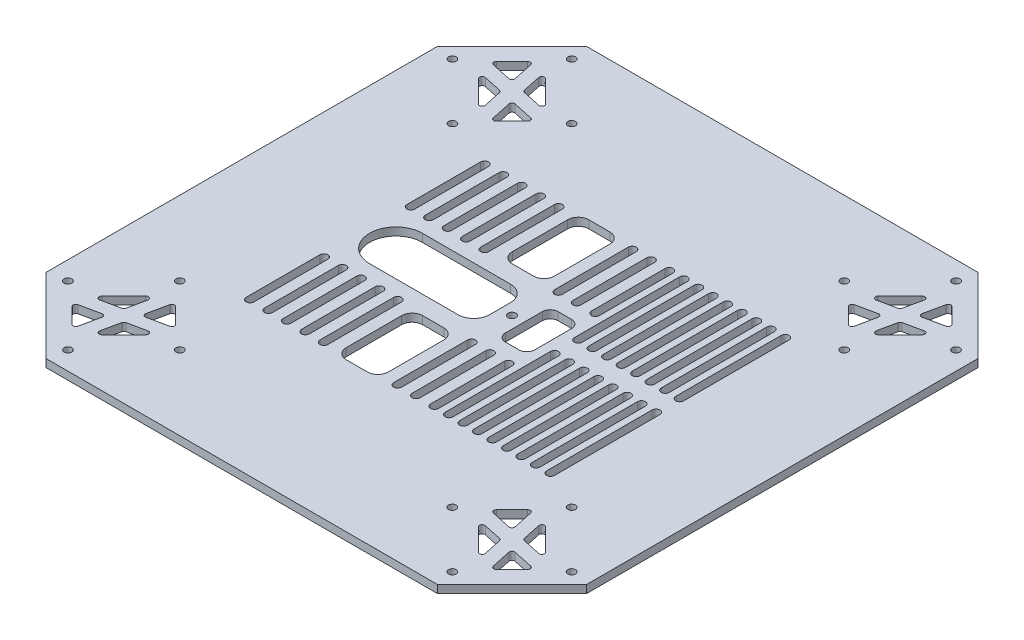
SolidWorks part; units mm, degrees
material "Thornel Mat VMA"
ref_plane "前视基准面" through (0, 0, 0) normal (0, 0, 1) x (1, 0, 0)
ref_plane "上视基准面" through (0, 0, 0) normal (0, 1, 0) x (1, 0, 0)
ref_plane "右视基准面" through (0, 0, 0) normal (1, 0, 0) x (0, 0, -1)
sketch "草图1" plane through (0, 0, 0) normal (0, 1, 0) x (1, 0, 0)
  line L0 (-74.2462, 102.5305) -> (-102.5305, 74.2462)
  line L1 (74.2462, 102.5305) -> (-74.2462, 102.5305)
  line L2 (102.5305, 74.2462) -> (102.5305, -74.2462)
  line L3 (74.2462, -102.5305) -> (-74.2462, -102.5305)
  line L4 (-102.5305, 74.2462) -> (-102.5305, -74.2462)
  line L5 (102.5305, 102.5305) -> (-102.5305, -102.5305) construction
  line L6 (102.5305, -102.5305) -> (-102.5305, 102.5305) construction
  line L7 (102.5305, -74.2462) -> (74.2462, -102.5305)
  line L8 (-102.5305, -74.2462) -> (-74.2462, -102.5305)
  line L9 (74.2462, 102.5305) -> (102.5305, 74.2462)
  line L10 (-102.5305, 102.5305) -> (-102.5305, -102.5305) construction
  line L11 (-102.5305, -102.5305) -> (102.5305, -102.5305) construction
  line L12 (102.5305, -102.5305) -> (102.5305, 102.5305) construction
  line L13 (102.5305, 102.5305) -> (-102.5305, 102.5305) construction
  point P0 (0, 0)
  dimension "D1" = 250
  dimension "D2" = 40
extrude "凸台-拉伸1" add sketch "草图1" along normal blind 3
hole_wizard "孔1" positions "草图4" profile "草图5" legacy
sketch "草图4" plane through (0, 3, 0) normal (0, 1, 0) x (1, 0, 0)
  point P0 (-95.5397, 72.9159)
  point P3 (-74.3265, 51.7027)
  point P6 (-51.6991, 74.3301)
  point P9 (-72.9123, 95.5433)
  point P16 (72.9159, 95.5397)
  point P17 (51.7027, 74.3265)
  point P18 (74.3301, 51.6991)
  point P19 (95.5433, 72.9123)
  point P20 (95.5397, -72.9159)
  point P21 (74.3265, -51.7027)
  point P22 (51.6991, -74.3301)
  point P23 (72.9123, -95.5433)
  point P24 (-72.9159, -95.5397)
  point P25 (-51.7027, -74.3265)
  point P26 (-74.3301, -51.6991)
  point P27 (-95.5433, -72.9123)
  dimension "D1" = 4
sketch "草图5" plane through (-95.5397, 3, -72.9159) normal (1, 0, 0) x (0, 0, 1)
  line L0 (0, 0) -> (0, 100)
  line L1 (0, 100) -> (1.45, 100)
  line L2 (1.45, 100) -> (1.45, 0)
  line L3 (1.45, 0) -> (0, 0)
  line L4 (0, 110) -> (0, -10) construction
  dimension "直径" = 2.9
  dimension "深度" = 100
sketch "草图7" plane through (0, 3, 0) normal (0, 1, 0) x (1, 0, 0)
  line L0 (-95.5397, 72.9159) -> (-51.6991, 74.3301) construction
  line L1 (-86.393, 80.4842) -> (-80.4806, 86.3966)
  line L2 (-84.1601, 71.4358) -> (-75.8066, 63.0823)
  line L3 (-71.4322, 84.1637) -> (-63.0787, 75.8102)
  line L4 (-66.7582, 60.8494) -> (-60.8458, 66.7618)
  line L5 (-89.8008, 77.0764) -> (-57.438, 70.1696) construction
  line L6 (-77.0728, 89.8044) -> (-70.166, 57.4416) construction
  line L7 (-49.2242, 67.6126) -> (-79.6109, 97.9993) construction
  line L8 (-74.2462, 102.5305) -> (-102.5305, 74.2462) construction
  line L9 (-85.8946, 78.7991) -> (-78.378, 77.1949)
  line L10 (-83.2443, 73.1208) -> (-76.36, 71.6516)
  line L11 (-87.6941, 79.1831) -> (-89.8008, 77.0764) construction
  line L12 (-89.8008, 77.0764) -> (-86.5509, 73.8265) construction
  line L13 (-60.6879, 73.4195) -> (-57.438, 70.1696) construction
  line L14 (-57.438, 70.1696) -> (-59.5447, 68.0629) construction
  line L15 (-67.4604, 74.8648) -> (-68.504, 69.975) construction
  line L16 (-73.6194, 73.623) -> (-67.2554, 79.987) construction
  line L17 (-74.1216, 63.9981) -> (-75.5908, 70.8824)
  line L18 (-68.4433, 61.3478) -> (-70.0475, 68.8644)
  line L19 (-70.8788, 75.5944) -> (-63.9945, 74.1252)
  line L20 (-77.1913, 78.3816) -> (-78.7955, 85.8982)
  line L21 (-68.8608, 70.0511) -> (-61.3442, 68.4469)
  line L22 (-71.648, 76.3636) -> (-73.1172, 83.2479)
  line L23 (80.4842, 86.393) -> (86.3966, 80.4806)
  line L24 (71.4358, 84.1601) -> (63.0823, 75.8066)
  line L25 (84.1637, 71.4322) -> (75.8102, 63.0787)
  line L26 (60.8494, 66.7582) -> (66.7618, 60.8458)
  line L27 (78.7991, 85.8946) -> (77.1949, 78.378)
  line L28 (73.1208, 83.2443) -> (71.6516, 76.36)
  line L29 (63.9981, 74.1216) -> (70.8824, 75.5908)
  line L30 (61.3478, 68.4433) -> (68.8644, 70.0475)
  line L31 (75.5944, 70.8788) -> (74.1252, 63.9945)
  line L32 (78.3816, 77.1913) -> (85.8982, 78.7955)
  line L33 (70.0511, 68.8608) -> (68.4469, 61.3442)
  line L34 (76.3636, 71.648) -> (83.2479, 73.1172)
  line L35 (72.9159, 95.5397) -> (74.3301, 51.6991) construction
  line L36 (77.0764, 89.8008) -> (70.1696, 57.438) construction
  line L37 (89.8044, 77.0728) -> (57.4416, 70.166) construction
  line L38 (79.1831, 87.6941) -> (77.0764, 89.8008) construction
  line L39 (77.0764, 89.8008) -> (73.8265, 86.5509) construction
  line L40 (73.4195, 60.6879) -> (70.1696, 57.438) construction
  line L41 (70.1696, 57.438) -> (68.0629, 59.5447) construction
  line L42 (74.8648, 67.4604) -> (69.975, 68.504) construction
  line L43 (73.623, 73.6194) -> (79.987, 67.2554) construction
  line L44 (86.393, -80.4842) -> (80.4806, -86.3966)
  line L45 (84.1601, -71.4358) -> (75.8066, -63.0823)
  line L46 (71.4322, -84.1637) -> (63.0787, -75.8102)
  line L47 (66.7582, -60.8494) -> (60.8458, -66.7618)
  line L48 (85.8946, -78.7991) -> (78.378, -77.1949)
  line L49 (83.2443, -73.1208) -> (76.36, -71.6516)
  line L50 (74.1216, -63.9981) -> (75.5908, -70.8824)
  line L51 (68.4433, -61.3478) -> (70.0475, -68.8644)
  line L52 (70.8788, -75.5944) -> (63.9945, -74.1252)
  line L53 (77.1913, -78.3816) -> (78.7955, -85.8982)
  line L54 (68.8608, -70.0511) -> (61.3442, -68.4469)
  line L55 (71.648, -76.3636) -> (73.1172, -83.2479)
  line L56 (95.5397, -72.9159) -> (51.6991, -74.3301) construction
  line L57 (89.8008, -77.0764) -> (57.438, -70.1696) construction
  line L58 (77.0728, -89.8044) -> (70.166, -57.4416) construction
  line L59 (87.6941, -79.1831) -> (89.8008, -77.0764) construction
  line L60 (89.8008, -77.0764) -> (86.5509, -73.8265) construction
  line L61 (60.6879, -73.4195) -> (57.438, -70.1696) construction
  line L62 (57.438, -70.1696) -> (59.5447, -68.0629) construction
  line L63 (67.4604, -74.8648) -> (68.504, -69.975) construction
  line L64 (73.6194, -73.623) -> (67.2554, -79.987) construction
  line L65 (-80.4842, -86.393) -> (-86.3966, -80.4806)
  line L66 (-71.4358, -84.1601) -> (-63.0823, -75.8066)
  line L67 (-84.1637, -71.4322) -> (-75.8102, -63.0787)
  line L68 (-60.8494, -66.7582) -> (-66.7618, -60.8458)
  line L69 (-78.7991, -85.8946) -> (-77.1949, -78.378)
  line L70 (-73.1208, -83.2443) -> (-71.6516, -76.36)
  line L71 (-63.9981, -74.1216) -> (-70.8824, -75.5908)
  line L72 (-61.3478, -68.4433) -> (-68.8644, -70.0475)
  line L73 (-75.5944, -70.8788) -> (-74.1252, -63.9945)
  line L74 (-78.3816, -77.1913) -> (-85.8982, -78.7955)
  line L75 (-70.0511, -68.8608) -> (-68.4469, -61.3442)
  line L76 (-76.3636, -71.648) -> (-83.2479, -73.1172)
  line L77 (-72.9159, -95.5397) -> (-74.3301, -51.6991) construction
  line L78 (-77.0764, -89.8008) -> (-70.1696, -57.438) construction
  line L79 (-89.8044, -77.0728) -> (-57.4416, -70.166) construction
  line L80 (-79.1831, -87.6941) -> (-77.0764, -89.8008) construction
  line L81 (-77.0764, -89.8008) -> (-73.8265, -86.5509) construction
  line L82 (-73.4195, -60.6879) -> (-70.1696, -57.438) construction
  line L83 (-70.1696, -57.438) -> (-68.0629, -59.5447) construction
  line L84 (-74.8648, -67.4604) -> (-69.975, -68.504) construction
  line L85 (-73.623, -73.6194) -> (-79.987, -67.2554) construction
  arc A0 (-63.0787, 75.8102) -> (-63.9945, 74.1252) centre (-63.7858, 75.1031) cw
  arc A1 (-70.8788, 75.5944) -> (-71.648, 76.3636) centre (-70.67, 76.5724) cw
  arc A2 (-71.4322, 84.1637) -> (-73.1172, 83.2479) centre (-72.1393, 83.4566) ccw
  arc A3 (-78.7955, 85.8982) -> (-80.4806, 86.3966) centre (-79.7735, 85.6895) ccw
  arc A4 (-85.8946, 78.7991) -> (-86.393, 80.4842) centre (-85.6859, 79.7771) cw
  arc A5 (-78.378, 77.1949) -> (-77.1913, 78.3816) centre (-78.1693, 78.1729) ccw
  arc A6 (-66.7582, 60.8494) -> (-68.4433, 61.3478) centre (-67.4653, 61.5565) cw
  arc A7 (-60.8458, 66.7618) -> (-61.3442, 68.4469) centre (-61.5529, 67.4689) ccw
  arc A8 (-68.8608, 70.0511) -> (-70.0475, 68.8644) centre (-69.0695, 69.0731) ccw
  arc A9 (-75.8066, 63.0823) -> (-74.1216, 63.9981) centre (-75.0995, 63.7894) ccw
  arc A10 (-75.5908, 70.8824) -> (-76.36, 71.6516) centre (-76.5688, 70.6736) ccw
  arc A11 (-83.2443, 73.1208) -> (-84.1601, 71.4358) centre (-83.453, 72.1429) ccw
  arc A12 (75.8102, 63.0787) -> (74.1252, 63.9945) centre (75.1031, 63.7858) cw
  arc A13 (75.5944, 70.8788) -> (76.3636, 71.648) centre (76.5724, 70.67) cw
  arc A14 (84.1637, 71.4322) -> (83.2479, 73.1172) centre (83.4566, 72.1393) ccw
  arc A15 (85.8982, 78.7955) -> (86.3966, 80.4806) centre (85.6895, 79.7735) ccw
  arc A16 (78.7991, 85.8946) -> (80.4842, 86.393) centre (79.7771, 85.6859) cw
  arc A17 (77.1949, 78.378) -> (78.3816, 77.1913) centre (78.1729, 78.1693) ccw
  arc A18 (60.8494, 66.7582) -> (61.3478, 68.4433) centre (61.5565, 67.4653) cw
  arc A19 (66.7618, 60.8458) -> (68.4469, 61.3442) centre (67.4689, 61.5529) ccw
  arc A20 (70.0511, 68.8608) -> (68.8644, 70.0475) centre (69.0731, 69.0695) ccw
  arc A21 (63.0823, 75.8066) -> (63.9981, 74.1216) centre (63.7894, 75.0995) ccw
  arc A22 (70.8824, 75.5908) -> (71.6516, 76.36) centre (70.6736, 76.5688) ccw
  arc A23 (73.1208, 83.2443) -> (71.4358, 84.1601) centre (72.1429, 83.453) ccw
  arc A24 (63.0787, -75.8102) -> (63.9945, -74.1252) centre (63.7858, -75.1031) cw
  arc A25 (70.8788, -75.5944) -> (71.648, -76.3636) centre (70.67, -76.5724) cw
  arc A26 (71.4322, -84.1637) -> (73.1172, -83.2479) centre (72.1393, -83.4566) ccw
  arc A27 (78.7955, -85.8982) -> (80.4806, -86.3966) centre (79.7735, -85.6895) ccw
  arc A28 (85.8946, -78.7991) -> (86.393, -80.4842) centre (85.6859, -79.7771) cw
  arc A29 (78.378, -77.1949) -> (77.1913, -78.3816) centre (78.1693, -78.1729) ccw
  arc A30 (66.7582, -60.8494) -> (68.4433, -61.3478) centre (67.4653, -61.5565) cw
  arc A31 (60.8458, -66.7618) -> (61.3442, -68.4469) centre (61.5529, -67.4689) ccw
  arc A32 (68.8608, -70.0511) -> (70.0475, -68.8644) centre (69.0695, -69.0731) ccw
  arc A33 (75.8066, -63.0823) -> (74.1216, -63.9981) centre (75.0995, -63.7894) ccw
  arc A34 (75.5908, -70.8824) -> (76.36, -71.6516) centre (76.5688, -70.6736) ccw
  arc A35 (83.2443, -73.1208) -> (84.1601, -71.4358) centre (83.453, -72.1429) ccw
  arc A36 (-75.8102, -63.0787) -> (-74.1252, -63.9945) centre (-75.1031, -63.7858) cw
  arc A37 (-75.5944, -70.8788) -> (-76.3636, -71.648) centre (-76.5724, -70.67) cw
  arc A38 (-84.1637, -71.4322) -> (-83.2479, -73.1172) centre (-83.4566, -72.1393) ccw
  arc A39 (-85.8982, -78.7955) -> (-86.3966, -80.4806) centre (-85.6895, -79.7735) ccw
  arc A40 (-78.7991, -85.8946) -> (-80.4842, -86.393) centre (-79.7771, -85.6859) cw
  arc A41 (-77.1949, -78.378) -> (-78.3816, -77.1913) centre (-78.1729, -78.1693) ccw
  arc A42 (-60.8494, -66.7582) -> (-61.3478, -68.4433) centre (-61.5565, -67.4653) cw
  arc A43 (-66.7618, -60.8458) -> (-68.4469, -61.3442) centre (-67.4689, -61.5529) ccw
  arc A44 (-70.0511, -68.8608) -> (-68.8644, -70.0475) centre (-69.0731, -69.0695) ccw
  arc A45 (-63.0823, -75.8066) -> (-63.9981, -74.1216) centre (-63.7894, -75.0995) ccw
  arc A46 (-70.8824, -75.5908) -> (-71.6516, -76.36) centre (-70.6736, -76.5688) ccw
  arc A47 (-73.1208, -83.2443) -> (-71.4358, -84.1601) centre (-72.1429, -83.453) ccw
  point P5 (-73.6194, 73.623)
  point P14 (-72.9123, 95.5433)
  point P21 (-67.9822, 72.4199)
  point P38 (-71.5127, 75.7297)
  point P41 (-73.8229, 86.5545)
  point P44 (-79.1795, 87.6977)
  point P50 (-76.8693, 76.8729)
  point P53 (-68.0593, 59.5483)
  point P59 (-70.3695, 70.3731)
  point P62 (-73.4159, 60.6915)
  point P73 (73.623, 73.6194)
  point P84 (72.4199, 67.9822)
  point P126 (73.6194, -73.623)
  point P137 (67.9822, -72.4199)
  point P179 (-73.623, -73.6194)
  point P190 (-72.4199, -67.9822)
  point P230 (0, 0)
  dimension "D4" = 1
  dimension "D1" = 7
  dimension "D2" = 7
  dimension "D3" = 5
  dimension "D5" = 4
extrude "切除-拉伸2" cut sketch "草图7" against normal through all both and the other way through all
sketch "草图8" plane through (0, 3, 0) normal (0, 1, 0) x (1, 0, 0)
  line L0 (-208.5651, 0) -> (0, 0) construction
  line L1 (-102.5305, -74.2462) -> (-50.5427, 0) construction
  line L3 (0, 0) -> (-88.3883, -88.3883) construction
  line L4 (-102.5305, -74.2462) -> (-74.2462, -102.5305) construction
  line L5 (0, 102.5305) -> (0, -102.5305) construction
  line L6 (74.2462, 102.5305) -> (-74.2462, 102.5305) construction
  line L7 (-74.2462, -102.5305) -> (74.2462, -102.5305) construction
  circle A0 centre (-208.5651, 0) radius 129.4443
  circle A2 centre (0, 208.5651) radius 129.4443
  circle A3 centre (208.5651, 0) radius 129.4443
  circle A4 centre (0, -208.5651) radius 129.4443
  point P28 (0, 0)
  dimension "D1" = 10
  dimension "D2" = 4
extrude "切除-拉伸3" cut sketch "草图8" against normal through all both and the other way through all
sketch "草图12" plane through (0, 3, 0) normal (0, 1, 0) x (1, 0, 0)
  line L0 (-74.2462, 102.5305) -> (-19.9669, 133.265)
  line L1 (-17.0105, 134.0438) -> (17.0105, 134.0438)
  line L2 (19.9669, 133.265) -> (74.2462, 102.5305)
  line L3 (0, 134.0438) -> (0, 0) construction
  line L4 (-74.2462, 102.5305) -> (-66.3304, 96.7253)
  line L5 (-62.6332, 98.7635) -> (-17.5957, 124.265)
  line L6 (-14.6394, 125.0438) -> (-10.5, 125.0438)
  line L7 (17.5957, 124.265) -> (62.6332, 98.7635)
  line L8 (66.1574, 95.9526) -> (74.2462, 102.5305)
  line L9 (-4.5, 119.0438) -> (-4.5, 81.2866)
  line L10 (-9.698, 64.0438) -> (9.698, 64.0438)
  line L11 (4.5, 81.2866) -> (4.5, 119.0438)
  line L12 (10.5, 125.0438) -> (14.6394, 125.0438)
  line L13 (-46.2735, 118.3694) -> (-41.839, 110.5377) construction
  line L14 (-4.5, 125.0438) -> (-4.5, 134.0438) construction
  line L15 (-66.3304, 96.7253) -> (-9.698, 64.0438)
  line L16 (9.698, 64.0438) -> (66.1574, 95.9526)
  line L17 (-4.5, 79.199) -> (4.5, 79.199) construction
  line L18 (-79.1207, 0) -> (79.1207, 0) construction
  line L19 (-4.5, -79.199) -> (4.5, -79.199) construction
  line L20 (-4.5, -125.0438) -> (-4.5, -134.0438) construction
  line L21 (-46.2735, -118.3694) -> (-41.839, -110.5377) construction
  line L22 (9.698, -64.0438) -> (66.1574, -95.9526)
  line L23 (-66.3304, -96.7253) -> (-9.698, -64.0438)
  line L24 (10.5, -125.0438) -> (14.6394, -125.0438)
  line L25 (4.5, -81.2866) -> (4.5, -119.0438)
  line L26 (-9.698, -64.0438) -> (9.698, -64.0438)
  line L27 (-4.5, -119.0438) -> (-4.5, -81.2866)
  line L28 (66.1574, -95.9526) -> (74.2462, -102.5305)
  line L29 (17.5957, -124.265) -> (62.6332, -98.7635)
  line L30 (-14.6394, -125.0438) -> (-10.5, -125.0438)
  line L31 (-62.6332, -98.7635) -> (-17.5957, -124.265)
  line L32 (-74.2462, -102.5305) -> (-66.3304, -96.7253)
  line L33 (19.9669, -133.265) -> (74.2462, -102.5305)
  line L34 (-17.0105, -134.0438) -> (17.0105, -134.0438)
  line L35 (-74.2462, -102.5305) -> (-19.9669, -133.265)
  arc A0 (-62.6152, 95.2727) -> (-6.602, 79.2892) centre (0, 208.5651) ccw
  arc A1 (-74.2462, 102.5305) -> (74.2462, 102.5305) centre (0, 208.5651) ccw construction
  arc A2 (6.602, 79.2892) -> (62.6152, 95.2727) centre (0, 208.5651) ccw
  arc A3 (-102.5305, -74.2462) -> (-102.5305, 74.2462) centre (-208.5651, 0) ccw construction
  arc A4 (102.5305, 74.2462) -> (102.5305, -74.2462) centre (208.5651, 0) ccw construction
  arc A5 (62.6152, 95.2727) -> (62.6332, 98.7635) centre (61.6478, 97.0231) ccw
  arc A6 (-62.6332, 98.7635) -> (-62.6152, 95.2727) centre (-61.6478, 97.0231) ccw
  arc A7 (6.602, 79.2892) -> (4.5, 81.2866) centre (6.5, 81.2866) cw
  arc A8 (-4.5, 81.2866) -> (-6.602, 79.2892) centre (-6.5, 81.2866) cw
  arc A9 (19.9669, 133.265) -> (17.0105, 134.0438) centre (17.0105, 128.0438) ccw
  arc A10 (-17.0105, 134.0438) -> (-19.9669, 133.265) centre (-17.0105, 128.0438) ccw
  arc A11 (-14.6394, 125.0438) -> (-17.5957, 124.265) centre (-14.6394, 119.0438) ccw
  arc A12 (17.5957, 124.265) -> (14.6394, 125.0438) centre (14.6394, 119.0438) ccw
  arc A13 (4.5, 119.0438) -> (10.5, 125.0438) centre (10.5, 119.0438) cw
  arc A14 (-4.5, 119.0438) -> (-10.5, 125.0438) centre (-10.5, 119.0438) ccw
  arc A15 (-4.5, -119.0438) -> (-10.5, -125.0438) centre (-10.5, -119.0438) cw
  arc A16 (4.5, -119.0438) -> (10.5, -125.0438) centre (10.5, -119.0438) ccw
  arc A17 (17.5957, -124.265) -> (14.6394, -125.0438) centre (14.6394, -119.0438) cw
  arc A18 (-14.6394, -125.0438) -> (-17.5957, -124.265) centre (-14.6394, -119.0438) cw
  arc A19 (-17.0105, -134.0438) -> (-19.9669, -133.265) centre (-17.0105, -128.0438) cw
  arc A20 (19.9669, -133.265) -> (17.0105, -134.0438) centre (17.0105, -128.0438) cw
  arc A21 (-4.5, -81.2866) -> (-6.602, -79.2892) centre (-6.5, -81.2866) ccw
  arc A22 (6.602, -79.2892) -> (4.5, -81.2866) centre (6.5, -81.2866) ccw
  arc A23 (-62.6332, -98.7635) -> (-62.6152, -95.2727) centre (-61.6478, -97.0231) cw
  arc A24 (62.6152, -95.2727) -> (62.6332, -98.7635) centre (61.6478, -97.0231) cw
  arc A25 (6.602, -79.2892) -> (62.6152, -95.2727) centre (0, -208.5651) cw
  arc A26 (-62.6152, -95.2727) -> (-6.602, -79.2892) centre (0, -208.5651) cw
  point P17 (0, 64.0438)
  point P24 (0, 79.199)
  point P40 (65.6946, 97.0301)
  point P43 (-65.6946, 97.0301)
  point P60 (4.5, 125.0438)
  point P107 (4.5, -125.0438)
  point P108 (-65.6946, -97.0301)
  point P109 (65.6946, -97.0301)
  point P110 (0, -79.199)
  point P111 (0, -64.0438)
  dimension "D4" = 2
  dimension "D5" = 2
  dimension "D6" = 6
  dimension "D1" = 70
  dimension "D2" = 9
  dimension "D3" = 9
sketch "草图15" plane through (0, 3, 0) normal (0, 1, 0) x (1, 0, 0)
  line L1 (-40.3412, 82.6837) -> (-31.9185, 62.6852)
  line L2 (44.6358, 80.4465) -> (36.2732, 60.2701)
  line L3 (-42.4295, -81.6317) -> (-34.5316, -61.2845)
  line L4 (41.391, -82.1632) -> (34.5498, -61.2743)
  arc A0 (-42.4295, -81.6317) -> (41.391, -82.1632) centre (0, 0) ccw
  arc A2 (-34.5316, -61.2845) -> (34.5498, -61.2743) centre (0, 0) ccw
  arc A3 (36.2732, 60.2701) -> (-31.9185, 62.6852) centre (0, 0) ccw
  arc A4 (44.6358, 80.4465) -> (-40.3412, 82.6837) centre (0, 0) ccw
  dimension "D1" = 92
extrude "凸台-拉伸3" add sketch "草图15" against normal up to surface (3 mm away) up to face at (-81.1939, 0, -81.1975)
sketch "草图18" plane through (0, 3, 0) normal (0, 1, 0) x (1, 0, 0)
  line L0 (-44.0207, 0) -> (12.6253, 0) construction
  line L1 (-44.0207, 10) -> (-10.5, 10)
  line L2 (-44.0207, -10) -> (-10.5, -10)
  line L3 (-54.0207, 0) -> (-79.1207, 0) construction
  line L5 (-4.5, -10) -> (4.5, -10) construction
  line L6 (-4.5, 4) -> (-4.5, -4)
  line L9 (-4.5, 10) -> (4.5, -10) construction
  line L10 (-4.5, -10) -> (4.5, 10) construction
  line L11 (-4.5, 10) -> (4.5, 10) construction
  arc A0 (-44.0207, 10) -> (-44.0207, -10) centre (-44.0207, 0) ccw
  arc A2 (102.5305, 74.2462) -> (102.5305, -74.2462) centre (208.5651, 0) ccw construction
  arc A3 (-10.5, 10) -> (-4.5, 4) centre (-10.5, 4) cw
  arc A4 (-102.5305, -74.2462) -> (-102.5305, 74.2462) centre (-208.5651, 0) ccw construction
  arc A8 (-4.5, -4) -> (-10.5, -10) centre (-10.5, -4) cw
  circle A9 centre (0, 0) radius 1.5
  point P3 (0, 0)
  point P5 (0, 0)
  point P9 (79.1207, 0)
  point P14 (-54.0207, 0)
  point P15 (0, 0)
  dimension "D5" = 6
extrude "切除-拉伸5" cut sketch "草图18" against normal through all both and the other way through all
sketch "草图20" plane through (0, 0, 0) normal (0, -1, 0) x (1, 0, 0)
  line L0 (-45.8783, 0) -> (59.1207, 0) construction
  line L1 (59.1207, 44.5) -> (59.1207, 4.5) construction
  line L2 (60.6207, 44.5) -> (60.6207, 4.5)
  line L3 (57.6207, 44.5) -> (57.6207, 4.5)
  line L4 (59.1207, -44.5) -> (59.1207, -4.5) construction
  line L5 (60.6207, -44.5) -> (60.6207, -4.5)
  line L6 (57.6207, -44.5) -> (57.6207, -4.5)
  line L7 (53.6207, 44.5) -> (53.6207, 4.5) construction
  line L8 (55.1207, 44.5) -> (55.1207, 4.5)
  line L9 (52.1207, 44.5) -> (52.1207, 4.5)
  line L10 (53.6207, -44.5) -> (53.6207, -4.5) construction
  line L11 (55.1207, -44.5) -> (55.1207, -4.5)
  line L12 (52.1207, -44.5) -> (52.1207, -4.5)
  line L13 (48.1207, 44.5) -> (48.1207, 4.5) construction
  line L14 (49.6207, 44.5) -> (49.6207, 4.5)
  line L15 (46.6207, 44.5) -> (46.6207, 4.5)
  line L16 (48.1207, -44.5) -> (48.1207, -4.5) construction
  line L17 (49.6207, -44.5) -> (49.6207, -4.5)
  line L18 (46.6207, -44.5) -> (46.6207, -4.5)
  line L19 (42.6207, 44.5) -> (42.6207, 4.5) construction
  line L20 (44.1207, 44.5) -> (44.1207, 4.5)
  line L21 (41.1207, 44.5) -> (41.1207, 4.5)
  line L22 (42.6207, -44.5) -> (42.6207, -4.5) construction
  line L23 (44.1207, -44.5) -> (44.1207, -4.5)
  line L24 (41.1207, -44.5) -> (41.1207, -4.5)
  line L25 (37.1207, 44.5) -> (37.1207, 4.5) construction
  line L26 (38.6207, 44.5) -> (38.6207, 4.5)
  line L27 (35.6207, 44.5) -> (35.6207, 4.5)
  line L28 (37.1207, -44.5) -> (37.1207, -4.5) construction
  line L29 (38.6207, -44.5) -> (38.6207, -4.5)
  line L30 (35.6207, -44.5) -> (35.6207, -4.5)
  line L31 (31.6207, 44.5) -> (31.6207, 4.5) construction
  line L32 (33.1207, 44.5) -> (33.1207, 4.5)
  line L33 (30.1207, 44.5) -> (30.1207, 4.5)
  line L34 (31.6207, -44.5) -> (31.6207, -4.5) construction
  line L35 (33.1207, -44.5) -> (33.1207, -4.5)
  line L36 (30.1207, -44.5) -> (30.1207, -4.5)
  line L37 (26.1207, 44.5) -> (26.1207, 4.5) construction
  line L38 (27.6207, 44.5) -> (27.6207, 4.5)
  line L39 (24.6207, 44.5) -> (24.6207, 4.5)
  line L40 (26.1207, -44.5) -> (26.1207, -4.5) construction
  line L41 (27.6207, -44.5) -> (27.6207, -4.5)
  line L42 (24.6207, -44.5) -> (24.6207, -4.5)
  line L43 (20.6207, 44.5) -> (20.6207, 4.5) construction
  line L44 (22.1207, 44.5) -> (22.1207, 4.5)
  line L45 (19.1207, 44.5) -> (19.1207, 4.5)
  line L46 (20.6207, -44.5) -> (20.6207, -4.5) construction
  line L47 (22.1207, -44.5) -> (22.1207, -4.5)
  line L48 (19.1207, -44.5) -> (19.1207, -4.5)
  line L238 (15.1207, -44.5) -> (15.1207, -4.5) construction
  line L239 (13.6207, -44.5) -> (13.6207, -4.5) [skipped]
  line L240 (16.6207, -44.5) -> (16.6207, -4.5) [skipped]
  line L241 (15.1207, 44.5) -> (15.1207, 4.5) construction
  line L242 (16.6207, 44.5) -> (16.6207, 4.5) [skipped]
  line L243 (13.6207, 44.5) -> (13.6207, 4.5) [skipped]
  line L244 (15.1207, -44.5) -> (15.1207, -4.5) construction
  line L245 (13.6207, -44.5) -> (13.6207, -4.5) [skipped]
  line L246 (16.6207, -44.5) -> (16.6207, -4.5) [skipped]
  line L247 (15.1207, 44.5) -> (15.1207, 4.5) construction
  line L248 (16.6207, 44.5) -> (16.6207, 4.5) [skipped]
  line L249 (13.6207, 44.5) -> (13.6207, 4.5) [skipped]
  arc A0 (60.6207, 44.5) -> (57.6207, 44.5) centre (59.1207, 44.5) ccw
  arc A1 (57.6207, 4.5) -> (60.6207, 4.5) centre (59.1207, 4.5) ccw
  arc A2 (60.6207, -44.5) -> (57.6207, -44.5) centre (59.1207, -44.5) cw
  arc A3 (57.6207, -4.5) -> (60.6207, -4.5) centre (59.1207, -4.5) cw
  arc A4 (55.1207, 44.5) -> (52.1207, 44.5) centre (53.6207, 44.5) ccw
  arc A5 (52.1207, 4.5) -> (55.1207, 4.5) centre (53.6207, 4.5) ccw
  arc A6 (55.1207, -44.5) -> (52.1207, -44.5) centre (53.6207, -44.5) cw
  arc A7 (52.1207, -4.5) -> (55.1207, -4.5) centre (53.6207, -4.5) cw
  arc A8 (49.6207, 44.5) -> (46.6207, 44.5) centre (48.1207, 44.5) ccw
  arc A9 (46.6207, 4.5) -> (49.6207, 4.5) centre (48.1207, 4.5) ccw
  arc A10 (49.6207, -44.5) -> (46.6207, -44.5) centre (48.1207, -44.5) cw
  arc A11 (46.6207, -4.5) -> (49.6207, -4.5) centre (48.1207, -4.5) cw
  arc A12 (44.1207, 44.5) -> (41.1207, 44.5) centre (42.6207, 44.5) ccw
  arc A13 (41.1207, 4.5) -> (44.1207, 4.5) centre (42.6207, 4.5) ccw
  arc A14 (44.1207, -44.5) -> (41.1207, -44.5) centre (42.6207, -44.5) cw
  arc A15 (41.1207, -4.5) -> (44.1207, -4.5) centre (42.6207, -4.5) cw
  arc A16 (38.6207, 44.5) -> (35.6207, 44.5) centre (37.1207, 44.5) ccw
  arc A17 (35.6207, 4.5) -> (38.6207, 4.5) centre (37.1207, 4.5) ccw
  arc A18 (38.6207, -44.5) -> (35.6207, -44.5) centre (37.1207, -44.5) cw
  arc A19 (35.6207, -4.5) -> (38.6207, -4.5) centre (37.1207, -4.5) cw
  arc A20 (33.1207, 44.5) -> (30.1207, 44.5) centre (31.6207, 44.5) ccw
  arc A21 (30.1207, 4.5) -> (33.1207, 4.5) centre (31.6207, 4.5) ccw
  arc A22 (33.1207, -44.5) -> (30.1207, -44.5) centre (31.6207, -44.5) cw
  arc A23 (30.1207, -4.5) -> (33.1207, -4.5) centre (31.6207, -4.5) cw
  arc A24 (27.6207, 44.5) -> (24.6207, 44.5) centre (26.1207, 44.5) ccw
  arc A25 (24.6207, 4.5) -> (27.6207, 4.5) centre (26.1207, 4.5) ccw
  arc A26 (27.6207, -44.5) -> (24.6207, -44.5) centre (26.1207, -44.5) cw
  arc A27 (24.6207, -4.5) -> (27.6207, -4.5) centre (26.1207, -4.5) cw
  arc A28 (22.1207, 44.5) -> (19.1207, 44.5) centre (20.6207, 44.5) ccw
  arc A29 (19.1207, 4.5) -> (22.1207, 4.5) centre (20.6207, 4.5) ccw
  arc A30 (22.1207, -44.5) -> (19.1207, -44.5) centre (20.6207, -44.5) cw
  arc A31 (19.1207, -4.5) -> (22.1207, -4.5) centre (20.6207, -4.5) cw
  arc A32 (102.5305, 74.2462) -> (102.5305, -74.2462) centre (208.5651, 0) ccw construction
  arc A162 (13.6207, -44.5) -> (16.6207, -44.5) centre (15.1207, -44.5) ccw [skipped]
  arc A163 (16.6207, -4.5) -> (13.6207, -4.5) centre (15.1207, -4.5) ccw [skipped]
  arc A164 (16.6207, 44.5) -> (13.6207, 44.5) centre (15.1207, 44.5) ccw [skipped]
  arc A165 (13.6207, 4.5) -> (16.6207, 4.5) centre (15.1207, 4.5) ccw [skipped]
  point P5 (59.1207, 24.5)
  point P11 (59.1207, 3)
  point P13 (59.1207, -24.5)
  point P18 (59.1207, -3)
  point P19 (79.1207, 0)
  point P20 (16.0965, -28.5688)
  point P23 (53.6207, 24.5)
  point P29 (53.6207, 3)
  point P31 (53.6207, -24.5)
  point P36 (53.6207, -3)
  point P39 (48.1207, 24.5)
  point P45 (48.1207, 3)
  point P47 (48.1207, -24.5)
  point P52 (48.1207, -3)
  point P55 (42.6207, 24.5)
  point P61 (42.6207, 3)
  point P63 (42.6207, -24.5)
  point P68 (42.6207, -3)
  point P71 (37.1207, 24.5)
  point P77 (37.1207, 3)
  point P79 (37.1207, -24.5)
  point P84 (37.1207, -3)
  point P87 (31.6207, 24.5)
  point P93 (31.6207, 3)
  point P95 (31.6207, -24.5)
  point P100 (31.6207, -3)
  point P103 (26.1207, 24.5)
  point P109 (26.1207, 3)
  point P111 (26.1207, -24.5)
  point P116 (26.1207, -3)
  point P119 (20.6207, 24.5)
  point P125 (20.6207, 3)
  point P127 (20.6207, -24.5)
  point P132 (20.6207, -3)
  point P135 (21.0655, -24.0622)
  point P140 (15.1207, -3)
  point P142 (15.1207, 3)
  point P149 (21.0655, 24.0622)
  point P157 (21.0655, -24.0622)
  point P164 (21.0655, 24.0622)
  point P171 (21.0655, -24.0622)
  point P178 (21.0655, 24.0622)
  point P185 (21.0655, -24.0622)
  point P192 (21.0655, 24.0622)
  point P199 (21.0655, -24.0622)
  point P206 (21.0655, 24.0622)
  point P213 (21.0655, -24.0622)
  point P220 (21.0655, 24.0622)
  point P227 (16.1207, -24.0622)
  point P234 (16.1207, 24.0622)
  point P241 (16.1207, -24.0622)
  point P248 (16.1207, 24.0622)
  point P255 (11.1207, -24.0622)
  point P262 (11.1207, 24.0622)
  point P269 (11.1207, -24.0622)
  point P276 (11.1207, 24.0622)
  point P283 (11.1207, -29.0622)
  point P290 (11.1207, 29.0622)
  point P297 (11.1207, -29.0622)
  point P304 (11.1207, 29.0622)
  point P311 (15.1207, -29)
  point P318 (15.1207, 29)
  point P325 (15.1207, -29)
  point P332 (15.1207, 29)
  point P339 (15.1207, -24)
  point P346 (15.1207, 24)
  point P353 (15.1207, -24)
  point P360 (15.1207, 24)
  point P367 (15.1207, -24.5)
  point P374 (15.1207, 24.5)
  point P381 (15.1207, -24.5)
  point P388 (15.1207, 24.5)
  point P395 (15.1207, -24.5)
  point P402 (15.1207, 24.5)
  point P409 (15.1207, -24.5)
  point P416 (15.1207, 24.5)
  point P423 (15.1207, -24.5)
  point P430 (15.1207, 24.5)
  point P437 (15.1207, -24.5)
  point P444 (15.1207, 24.5)
  point P451 (15.1207, -24.5)
  point P458 (15.1207, 24.5)
  point P465 (15.1207, -24.5)
  point P472 (15.1207, 24.5)
  point P479 (15.1207, -24.5)
  point P486 (15.1207, 24.5)
  point P493 (15.1207, -24.5)
  point P500 (15.1207, 24.5)
  point P507 (15.1207, -24.5)
  point P514 (15.1207, 24.5)
  point P521 (15.1207, -24.5)
  point P528 (15.1207, 24.5)
  point P535 (15.1207, -24.5)
  point P542 (15.1207, 24.5)
  point P549 (15.1207, -24.5)
  point P556 (15.1207, 24.5)
  point P563 (15.1207, -24.5)
  point P570 (15.1207, 24.5)
  point P577 (15.1207, -24.5)
  point P584 (15.1207, 24.5)
  point P591 (15.1207, -24.5)
  point P598 (15.1207, 24.5)
  dimension "D2" = 9
  dimension "D5" = 1.5
  dimension "D1" = 3
  dimension "D3" = 40
  dimension "D4" = 20
  dimension "D6" = 5.5
extrude "切除-拉伸7" cut sketch "草图20" against normal through all both and the other way through all
sketch "草图21" plane through (0, 3, 0) normal (0, 1, 0) x (1, 0, 0)
  line L0 (15.1207, 16.5) -> (15.1207, 44.5) construction
  line L1 (13.6207, 16.5) -> (13.6207, 44.5)
  line L2 (16.6207, 16.5) -> (16.6207, 44.5)
  line L3 (15.1207, 44.5) -> (20.6207, 44.5) construction
  line L4 (19.1207, 4.5) -> (19.1207, 44.5) construction
  line L5 (-13.3448, 10) -> (19.1207, 10) construction
  line L6 (-10.5, 10) -> (-44.0207, 10) construction
  line L7 (0, 0) -> (29.0659, 0) construction
  line L8 (15.1207, -16.5) -> (15.1207, -44.5) construction
  line L9 (16.6207, -16.5) -> (16.6207, -44.5)
  line L10 (13.6207, -16.5) -> (13.6207, -44.5)
  line L12 (8.1207, 44.5) -> (13.6207, 44.5) construction
  line L14 (8.1207, 16.5) -> (8.1207, 44.5) construction
  line L15 (6.6207, 16.5) -> (6.6207, 44.5)
  line L16 (9.6207, 16.5) -> (9.6207, 44.5)
  line L17 (8.1207, -16.5) -> (8.1207, -44.5) construction
  line L18 (9.6207, -16.5) -> (9.6207, -44.5)
  line L19 (6.6207, -16.5) -> (6.6207, -44.5)
  line L20 (1.1207, 44.5) -> (6.6207, 44.5) construction
  line L21 (6.6207, -44.5) -> (1.1207, -44.5) construction
  line L22 (1.1207, 16.5) -> (1.1207, 44.5) construction
  line L23 (-0.3793, 16.5) -> (-0.3793, 44.5)
  line L24 (2.6207, 16.5) -> (2.6207, 44.5)
  line L25 (1.1207, -16.5) -> (1.1207, -44.5) construction
  line L26 (2.6207, -16.5) -> (2.6207, -44.5)
  line L27 (-0.3793, -16.5) -> (-0.3793, -44.5)
  line L28 (-5.8793, 44.5) -> (-0.3793, 44.5) construction
  line L29 (-0.3793, -44.5) -> (-5.8793, -44.5) construction
  line L52 (-26.8793, 44.5) -> (-21.3793, 44.5) construction
  line L53 (-21.3793, -44.5) -> (-26.8793, -44.5) construction
  line L54 (-33.8793, 44.5) -> (-28.3793, 44.5) construction
  line L55 (-28.3793, -44.5) -> (-33.8793, -44.5) construction
  line L56 (-7, 0) -> (22.0659, 0) construction
  line L57 (-26.8793, 16.5) -> (-26.8793, 44.5) construction
  line L58 (-28.3793, 16.5) -> (-28.3793, 44.5)
  line L59 (-25.3793, 16.5) -> (-25.3793, 44.5)
  line L60 (-26.8793, -16.5) -> (-26.8793, -44.5) construction
  line L61 (-25.3793, -16.5) -> (-25.3793, -44.5)
  line L62 (-28.3793, -16.5) -> (-28.3793, -44.5)
  line L63 (-40.8793, 44.5) -> (-35.3793, 44.5) construction
  line L64 (-35.3793, -44.5) -> (-40.8793, -44.5) construction
  line L65 (-14, 0) -> (15.0659, 0) construction
  line L66 (-33.8793, 16.5) -> (-33.8793, 44.5) construction
  line L67 (-35.3793, 16.5) -> (-35.3793, 44.5)
  line L68 (-32.3793, 16.5) -> (-32.3793, 44.5)
  line L69 (-33.8793, -16.5) -> (-33.8793, -44.5) construction
  line L70 (-32.3793, -16.5) -> (-32.3793, -44.5)
  line L71 (-35.3793, -16.5) -> (-35.3793, -44.5)
  line L72 (-47.8793, 44.5) -> (-42.3793, 44.5) construction
  line L73 (-42.3793, -44.5) -> (-47.8793, -44.5) construction
  line L74 (-21, 0) -> (8.0659, 0) construction
  line L75 (-40.8793, 16.5) -> (-40.8793, 44.5) construction
  line L76 (-42.3793, 16.5) -> (-42.3793, 44.5)
  line L77 (-39.3793, 16.5) -> (-39.3793, 44.5)
  line L78 (-40.8793, -16.5) -> (-40.8793, -44.5) construction
  line L79 (-39.3793, -16.5) -> (-39.3793, -44.5)
  line L80 (-42.3793, -16.5) -> (-42.3793, -44.5)
  line L81 (-54.8793, 44.5) -> (-49.3793, 44.5) construction
  line L82 (-49.3793, -44.5) -> (-54.8793, -44.5) construction
  line L83 (-28, 0) -> (1.0659, 0) construction
  line L84 (-47.8793, 16.5) -> (-47.8793, 44.5) construction
  line L85 (-49.3793, 16.5) -> (-49.3793, 44.5)
  line L86 (-46.3793, 16.5) -> (-46.3793, 44.5)
  line L87 (-47.8793, -16.5) -> (-47.8793, -44.5) construction
  line L88 (-46.3793, -16.5) -> (-46.3793, -44.5)
  line L89 (-49.3793, -16.5) -> (-49.3793, -44.5)
  line L90 (-61.8793, 44.5) -> (-56.3793, 44.5) construction
  line L91 (-56.3793, -44.5) -> (-61.8793, -44.5) construction
  line L92 (-35, 0) -> (-5.9341, 0) construction
  line L93 (-54.8793, 16.5) -> (-54.8793, 44.5) construction
  line L94 (-56.3793, 16.5) -> (-56.3793, 44.5)
  line L95 (-33.8793, 44.5) -> (-28.3793, 44.5) construction
  line L97 (-40.8793, 44.5) -> (-35.3793, 44.5) construction
  line L99 (-47.8793, 44.5) -> (-42.3793, 44.5) construction
  line L101 (-54.8793, 44.5) -> (-49.3793, 44.5) construction
  line L163 (-53.3793, 16.5) -> (-53.3793, 44.5)
  line L164 (-54.8793, -16.5) -> (-54.8793, -44.5) construction
  line L165 (-53.3793, -16.5) -> (-53.3793, -44.5)
  line L166 (-56.3793, -16.5) -> (-56.3793, -44.5)
  line L227 (-12.8793, 44.5) -> (-7.3793, 44.5) construction
  line L229 (-19.8793, 44.5) -> (-14.3793, 44.5) construction
  line L1000 (-5.8793, -16.5) -> (-5.8793, -44.5) construction
  line L1001 (-4.3793, -16.5) -> (-4.3793, -44.5) [skipped]
  line L1002 (-7.3793, -16.5) -> (-7.3793, -44.5) [skipped]
  line L1003 (-12.8793, 16.5) -> (-12.8793, 44.5) construction
  line L1004 (-14.3793, 16.5) -> (-14.3793, 44.5) [skipped]
  line L1005 (-11.3793, 16.5) -> (-11.3793, 44.5) [skipped]
  line L1006 (-12.8793, -16.5) -> (-12.8793, -44.5) construction
  line L1007 (-11.3793, -16.5) -> (-11.3793, -44.5) [skipped]
  line L1008 (-14.3793, -16.5) -> (-14.3793, -44.5) [skipped]
  line L1009 (-19.8793, 16.5) -> (-19.8793, 44.5) construction
  line L1010 (-21.3793, 16.5) -> (-21.3793, 44.5) [skipped]
  line L1011 (-18.3793, 16.5) -> (-18.3793, 44.5) [skipped]
  line L1012 (-19.8793, -16.5) -> (-19.8793, -44.5) construction
  line L1013 (-18.3793, -16.5) -> (-18.3793, -44.5) [skipped]
  line L1014 (-21.3793, -16.5) -> (-21.3793, -44.5) [skipped]
  line L1015 (-5.8793, 16.5) -> (-5.8793, 44.5) construction
  line L1016 (-7.3793, 16.5) -> (-7.3793, 44.5) [skipped]
  line L1017 (-4.3793, 16.5) -> (-4.3793, 44.5) [skipped]
  line L1018 (-26.8793, -16.5) -> (-26.8793, -44.5) construction
  line L1019 (-25.3793, -16.5) -> (-25.3793, -44.5) [skipped]
  line L1020 (-28.3793, -16.5) -> (-28.3793, -44.5) [skipped]
  line L1021 (-33.8793, 16.5) -> (-33.8793, 44.5) construction
  line L1022 (-35.3793, 16.5) -> (-35.3793, 44.5) [skipped]
  line L1023 (-32.3793, 16.5) -> (-32.3793, 44.5) [skipped]
  line L1024 (-33.8793, -16.5) -> (-33.8793, -44.5) construction
  line L1025 (-32.3793, -16.5) -> (-32.3793, -44.5) [skipped]
  line L1026 (-35.3793, -16.5) -> (-35.3793, -44.5) [skipped]
  line L1027 (-40.8793, 16.5) -> (-40.8793, 44.5) construction
  line L1028 (-42.3793, 16.5) -> (-42.3793, 44.5) [skipped]
  line L1029 (-39.3793, 16.5) -> (-39.3793, 44.5) [skipped]
  line L1030 (-40.8793, -16.5) -> (-40.8793, -44.5) construction
  line L1031 (-39.3793, -16.5) -> (-39.3793, -44.5) [skipped]
  line L1032 (-42.3793, -16.5) -> (-42.3793, -44.5) [skipped]
  line L1033 (-47.8793, 16.5) -> (-47.8793, 44.5) construction
  line L1034 (-49.3793, 16.5) -> (-49.3793, 44.5) [skipped]
  line L1035 (-46.3793, 16.5) -> (-46.3793, 44.5) [skipped]
  line L1036 (-47.8793, -16.5) -> (-47.8793, -44.5) construction
  line L1037 (-46.3793, -16.5) -> (-46.3793, -44.5) [skipped]
  line L1038 (-49.3793, -16.5) -> (-49.3793, -44.5) [skipped]
  line L1039 (-54.8793, 16.5) -> (-54.8793, 44.5) construction
  line L1040 (-56.3793, 16.5) -> (-56.3793, 44.5) [skipped]
  line L1041 (-53.3793, 16.5) -> (-53.3793, 44.5) [skipped]
  line L1042 (-54.8793, -16.5) -> (-54.8793, -44.5) construction
  line L1043 (-53.3793, -16.5) -> (-53.3793, -44.5) [skipped]
  line L1044 (-56.3793, -16.5) -> (-56.3793, -44.5) [skipped]
  line L1045 (-26.8793, 16.5) -> (-26.8793, 44.5) construction
  line L1046 (-28.3793, 16.5) -> (-28.3793, 44.5) [skipped]
  line L1047 (-25.3793, 16.5) -> (-25.3793, 44.5) [skipped]
  line L1048 (-5.8793, -16.5) -> (-5.8793, -44.5) construction
  line L1049 (-4.3793, -16.5) -> (-4.3793, -44.5) [skipped]
  line L1050 (-7.3793, -16.5) -> (-7.3793, -44.5) [skipped]
  line L1051 (-12.8793, 16.5) -> (-12.8793, 44.5) construction
  line L1052 (-14.3793, 16.5) -> (-14.3793, 44.5) [skipped]
  line L1053 (-11.3793, 16.5) -> (-11.3793, 44.5) [skipped]
  line L1054 (-12.8793, -16.5) -> (-12.8793, -44.5) construction
  line L1055 (-11.3793, -16.5) -> (-11.3793, -44.5) [skipped]
  line L1056 (-14.3793, -16.5) -> (-14.3793, -44.5) [skipped]
  line L1057 (-19.8793, 16.5) -> (-19.8793, 44.5) construction
  line L1058 (-21.3793, 16.5) -> (-21.3793, 44.5) [skipped]
  line L1059 (-18.3793, 16.5) -> (-18.3793, 44.5) [skipped]
  line L1060 (-19.8793, -16.5) -> (-19.8793, -44.5) construction
  line L1061 (-18.3793, -16.5) -> (-18.3793, -44.5) [skipped]
  line L1062 (-21.3793, -16.5) -> (-21.3793, -44.5) [skipped]
  line L1063 (-5.8793, 16.5) -> (-5.8793, 44.5) construction
  line L1064 (-7.3793, 16.5) -> (-7.3793, 44.5) [skipped]
  line L1065 (-4.3793, 16.5) -> (-4.3793, 44.5) [skipped]
  line L1066 (-26.8793, -16.5) -> (-26.8793, -44.5) construction
  line L1067 (-25.3793, -16.5) -> (-25.3793, -44.5) [skipped]
  line L1068 (-28.3793, -16.5) -> (-28.3793, -44.5) [skipped]
  line L1069 (-33.8793, 16.5) -> (-33.8793, 44.5) construction
  line L1070 (-35.3793, 16.5) -> (-35.3793, 44.5) [skipped]
  line L1071 (-32.3793, 16.5) -> (-32.3793, 44.5) [skipped]
  line L1072 (-33.8793, -16.5) -> (-33.8793, -44.5) construction
  line L1073 (-32.3793, -16.5) -> (-32.3793, -44.5) [skipped]
  line L1074 (-35.3793, -16.5) -> (-35.3793, -44.5) [skipped]
  line L1075 (-40.8793, 16.5) -> (-40.8793, 44.5) construction
  line L1076 (-42.3793, 16.5) -> (-42.3793, 44.5) [skipped]
  line L1077 (-39.3793, 16.5) -> (-39.3793, 44.5) [skipped]
  line L1078 (-40.8793, -16.5) -> (-40.8793, -44.5) construction
  line L1079 (-39.3793, -16.5) -> (-39.3793, -44.5) [skipped]
  line L1080 (-42.3793, -16.5) -> (-42.3793, -44.5) [skipped]
  line L1081 (-47.8793, 16.5) -> (-47.8793, 44.5) construction
  line L1082 (-49.3793, 16.5) -> (-49.3793, 44.5) [skipped]
  line L1083 (-46.3793, 16.5) -> (-46.3793, 44.5) [skipped]
  line L1084 (-47.8793, -16.5) -> (-47.8793, -44.5) construction
  line L1085 (-46.3793, -16.5) -> (-46.3793, -44.5) [skipped]
  line L1086 (-49.3793, -16.5) -> (-49.3793, -44.5) [skipped]
  line L1087 (-54.8793, 16.5) -> (-54.8793, 44.5) construction
  line L1088 (-56.3793, 16.5) -> (-56.3793, 44.5) [skipped]
  line L1089 (-53.3793, 16.5) -> (-53.3793, 44.5) [skipped]
  line L1090 (-54.8793, -16.5) -> (-54.8793, -44.5) construction
  line L1091 (-53.3793, -16.5) -> (-53.3793, -44.5) [skipped]
  line L1092 (-56.3793, -16.5) -> (-56.3793, -44.5) [skipped]
  line L1093 (-26.8793, 16.5) -> (-26.8793, 44.5) construction
  line L1094 (-28.3793, 16.5) -> (-28.3793, 44.5) [skipped]
  line L1095 (-25.3793, 16.5) -> (-25.3793, 44.5) [skipped]
  arc A0 (13.6207, 16.5) -> (16.6207, 16.5) centre (15.1207, 16.5) ccw
  arc A1 (16.6207, 44.5) -> (13.6207, 44.5) centre (15.1207, 44.5) ccw
  arc A2 (16.6207, -16.5) -> (13.6207, -16.5) centre (15.1207, -16.5) ccw
  arc A3 (13.6207, -44.5) -> (16.6207, -44.5) centre (15.1207, -44.5) ccw
  arc A5 (19.1207, -44.5) -> (22.1207, -44.5) centre (20.6207, -44.5) ccw construction
  arc A6 (6.6207, 16.5) -> (9.6207, 16.5) centre (8.1207, 16.5) ccw
  arc A7 (9.6207, 44.5) -> (6.6207, 44.5) centre (8.1207, 44.5) ccw
  arc A8 (9.6207, -16.5) -> (6.6207, -16.5) centre (8.1207, -16.5) ccw
  arc A9 (6.6207, -44.5) -> (9.6207, -44.5) centre (8.1207, -44.5) ccw
  arc A10 (-0.3793, 16.5) -> (2.6207, 16.5) centre (1.1207, 16.5) ccw
  arc A11 (2.6207, 44.5) -> (-0.3793, 44.5) centre (1.1207, 44.5) ccw
  arc A12 (2.6207, -16.5) -> (-0.3793, -16.5) centre (1.1207, -16.5) ccw
  arc A13 (-0.3793, -44.5) -> (2.6207, -44.5) centre (1.1207, -44.5) ccw
  arc A26 (-28.3793, 16.5) -> (-25.3793, 16.5) centre (-26.8793, 16.5) ccw
  arc A27 (-25.3793, 44.5) -> (-28.3793, 44.5) centre (-26.8793, 44.5) ccw
  arc A28 (-25.3793, -16.5) -> (-28.3793, -16.5) centre (-26.8793, -16.5) ccw
  arc A29 (-28.3793, -44.5) -> (-25.3793, -44.5) centre (-26.8793, -44.5) ccw
  arc A30 (-35.3793, 16.5) -> (-32.3793, 16.5) centre (-33.8793, 16.5) ccw
  arc A31 (-32.3793, 44.5) -> (-35.3793, 44.5) centre (-33.8793, 44.5) ccw
  arc A32 (-32.3793, -16.5) -> (-35.3793, -16.5) centre (-33.8793, -16.5) ccw
  arc A33 (-35.3793, -44.5) -> (-32.3793, -44.5) centre (-33.8793, -44.5) ccw
  arc A34 (-42.3793, 16.5) -> (-39.3793, 16.5) centre (-40.8793, 16.5) ccw
  arc A35 (-39.3793, 44.5) -> (-42.3793, 44.5) centre (-40.8793, 44.5) ccw
  arc A36 (-39.3793, -16.5) -> (-42.3793, -16.5) centre (-40.8793, -16.5) ccw
  arc A37 (-42.3793, -44.5) -> (-39.3793, -44.5) centre (-40.8793, -44.5) ccw
  arc A38 (-49.3793, 16.5) -> (-46.3793, 16.5) centre (-47.8793, 16.5) ccw
  arc A39 (-46.3793, 44.5) -> (-49.3793, 44.5) centre (-47.8793, 44.5) ccw
  arc A40 (-46.3793, -16.5) -> (-49.3793, -16.5) centre (-47.8793, -16.5) ccw
  arc A41 (-49.3793, -44.5) -> (-46.3793, -44.5) centre (-47.8793, -44.5) ccw
  arc A42 (-56.3793, 16.5) -> (-53.3793, 16.5) centre (-54.8793, 16.5) ccw
  arc A43 (-53.3793, 44.5) -> (-56.3793, 44.5) centre (-54.8793, 44.5) ccw
  arc A44 (-53.3793, -16.5) -> (-56.3793, -16.5) centre (-54.8793, -16.5) ccw
  arc A45 (-56.3793, -44.5) -> (-53.3793, -44.5) centre (-54.8793, -44.5) ccw
  arc A672 (-4.3793, -16.5) -> (-7.3793, -16.5) centre (-5.8793, -16.5) ccw [skipped]
  arc A673 (-7.3793, -44.5) -> (-4.3793, -44.5) centre (-5.8793, -44.5) ccw [skipped]
  arc A674 (-14.3793, 16.5) -> (-11.3793, 16.5) centre (-12.8793, 16.5) ccw [skipped]
  arc A675 (-11.3793, 44.5) -> (-14.3793, 44.5) centre (-12.8793, 44.5) ccw [skipped]
  arc A676 (-11.3793, -16.5) -> (-14.3793, -16.5) centre (-12.8793, -16.5) ccw [skipped]
  arc A677 (-14.3793, -44.5) -> (-11.3793, -44.5) centre (-12.8793, -44.5) ccw [skipped]
  arc A678 (-21.3793, 16.5) -> (-18.3793, 16.5) centre (-19.8793, 16.5) ccw [skipped]
  arc A679 (-18.3793, 44.5) -> (-21.3793, 44.5) centre (-19.8793, 44.5) ccw [skipped]
  arc A680 (-18.3793, -16.5) -> (-21.3793, -16.5) centre (-19.8793, -16.5) ccw [skipped]
  arc A681 (-21.3793, -44.5) -> (-18.3793, -44.5) centre (-19.8793, -44.5) ccw [skipped]
  arc A682 (-7.3793, 16.5) -> (-4.3793, 16.5) centre (-5.8793, 16.5) ccw [skipped]
  arc A683 (-4.3793, 44.5) -> (-7.3793, 44.5) centre (-5.8793, 44.5) ccw [skipped]
  arc A684 (-25.3793, -16.5) -> (-28.3793, -16.5) centre (-26.8793, -16.5) ccw [skipped]
  arc A685 (-28.3793, -44.5) -> (-25.3793, -44.5) centre (-26.8793, -44.5) ccw [skipped]
  arc A686 (-35.3793, 16.5) -> (-32.3793, 16.5) centre (-33.8793, 16.5) ccw [skipped]
  arc A687 (-32.3793, 44.5) -> (-35.3793, 44.5) centre (-33.8793, 44.5) ccw [skipped]
  arc A688 (-32.3793, -16.5) -> (-35.3793, -16.5) centre (-33.8793, -16.5) ccw [skipped]
  arc A689 (-35.3793, -44.5) -> (-32.3793, -44.5) centre (-33.8793, -44.5) ccw [skipped]
  arc A690 (-42.3793, 16.5) -> (-39.3793, 16.5) centre (-40.8793, 16.5) ccw [skipped]
  arc A691 (-39.3793, 44.5) -> (-42.3793, 44.5) centre (-40.8793, 44.5) ccw [skipped]
  arc A692 (-39.3793, -16.5) -> (-42.3793, -16.5) centre (-40.8793, -16.5) ccw [skipped]
  arc A693 (-42.3793, -44.5) -> (-39.3793, -44.5) centre (-40.8793, -44.5) ccw [skipped]
  arc A694 (-49.3793, 16.5) -> (-46.3793, 16.5) centre (-47.8793, 16.5) ccw [skipped]
  arc A695 (-46.3793, 44.5) -> (-49.3793, 44.5) centre (-47.8793, 44.5) ccw [skipped]
  arc A696 (-46.3793, -16.5) -> (-49.3793, -16.5) centre (-47.8793, -16.5) ccw [skipped]
  arc A697 (-49.3793, -44.5) -> (-46.3793, -44.5) centre (-47.8793, -44.5) ccw [skipped]
  arc A698 (-56.3793, 16.5) -> (-53.3793, 16.5) centre (-54.8793, 16.5) ccw [skipped]
  arc A699 (-53.3793, 44.5) -> (-56.3793, 44.5) centre (-54.8793, 44.5) ccw [skipped]
  arc A700 (-53.3793, -16.5) -> (-56.3793, -16.5) centre (-54.8793, -16.5) ccw [skipped]
  arc A701 (-56.3793, -44.5) -> (-53.3793, -44.5) centre (-54.8793, -44.5) ccw [skipped]
  arc A702 (-28.3793, 16.5) -> (-25.3793, 16.5) centre (-26.8793, 16.5) ccw [skipped]
  arc A703 (-25.3793, 44.5) -> (-28.3793, 44.5) centre (-26.8793, 44.5) ccw [skipped]
  point P2 (15.1207, 30.5)
  point P7 (20.6207, 44.5)
  point P13 (15.1207, 15)
  point P23 (15.1207, -30.5)
  point P31 (0, 0)
  point P37 (8.1207, 30.5)
  point P42 (13.6207, 44.5)
  point P45 (8.1207, 15)
  point P47 (8.1207, -30.5)
  point P56 (1.1207, 30.5)
  point P61 (6.6207, 44.5)
  point P64 (1.1207, 15)
  point P66 (1.1207, -30.5)
  point P76 (-5.8793, -30.5)
  point P80 (-0.3793, 44.5)
  point P85 (-12.8793, 30.5)
  point P93 (-21.3793, 44.5)
  point P95 (-12.8793, -30.5)
  point P99 (-5.8793, 15)
  point P101 (-19.8793, 15)
  point P102 (-7.3793, 44.5)
  point P104 (-19.8793, 30.5)
  point P109 (-14.3793, 44.5)
  point P110 (-12.8793, 15)
  point P114 (-19.8793, -30.5)
  point P133 (-26.8793, -30.5)
  point P136 (-26.8793, 30.5)
  point P142 (-33.8793, 30.5)
  point P145 (-26.8793, 15)
  point P149 (-26.8793, -30.5)
  point P150 (-54.8793, 15)
  point P152 (-33.8793, -30.5)
  point P156 (-26.8793, 15)
  point P158 (-49.3793, 44.5)
  point P159 (-28.3793, 44.5)
  point P160 (-28.3793, 44.5)
  point P161 (-40.8793, 30.5)
  point P166 (-47.8793, 15)
  point P167 (-42.3793, 44.5)
  point P169 (-40.8793, 15)
  point P171 (-40.8793, -30.5)
  point P173 (-33.8793, 30.5)
  point P175 (-33.8793, 15)
  point P177 (-35.3793, 44.5)
  point P180 (-47.8793, 30.5)
  point P182 (-33.8793, 15)
  point P184 (-33.8793, -30.5)
  point P190 (-47.8793, -30.5)
  point P191 (-35.3793, 44.5)
  point P199 (-54.8793, 30.5)
  point P200 (-40.8793, 30.5)
  point P206 (-40.8793, 15)
  point P208 (-40.8793, -30.5)
  point P209 (-54.8793, -30.5)
  point P215 (-42.3793, 44.5)
  point P223 (-47.8793, 30.5)
  point P225 (-26.8793, 30.5)
  point P230 (-47.8793, 15)
  point P232 (-47.8793, -30.5)
  point P251 (-5.8793, 30.5)
  point P253 (-26.8793, -30.5)
  point P260 (-33.8793, 30.5)
  point P267 (-33.8793, -30.5)
  point P274 (-40.8793, 30.5)
  point P276 (0, 0)
  point P277 (0, 0)
  point P278 (0, 0)
  point P281 (-40.8793, -30.5)
  point P288 (-47.8793, 30.5)
  point P295 (-47.8793, -30.5)
  point P302 (-54.8793, 30.5)
  point P309 (-54.8793, -30.5)
  point P316 (-26.8793, 30.5)
  point P323 (-26.8793, -30.5)
  point P330 (-33.8793, 30.5)
  point P337 (-33.8793, -30.5)
  point P344 (-40.8793, 30.5)
  point P351 (-40.8793, -30.5)
  point P358 (-47.8793, 30.5)
  point P365 (-47.8793, -30.5)
  point P372 (-54.8793, 30.5)
  point P379 (-54.8793, -30.5)
  point P386 (-26.8793, 30.5)
  point P394 (-49.3793, 44.5)
  point P402 (-54.8793, 30.5)
  point P408 (-54.8793, 15)
  point P410 (-54.8793, -30.5)
  point P416 (-56.3793, 44.5)
  point P422 (-26.8793, -30.5)
  point P429 (-33.8793, 30.5)
  point P436 (-33.8793, -30.5)
  point P443 (-40.8793, 30.5)
  point P450 (-40.8793, -30.5)
  point P457 (-47.8793, 30.5)
  point P464 (-47.8793, -30.5)
  point P471 (-54.8793, 30.5)
  point P478 (-54.8793, -30.5)
  point P485 (-26.8793, 30.5)
  point P492 (-26.8793, -30.5)
  point P499 (-33.8793, 30.5)
  point P506 (-33.8793, -30.5)
  point P513 (-40.8793, 30.5)
  point P520 (-40.8793, -30.5)
  point P527 (-47.8793, 30.5)
  point P534 (-47.8793, -30.5)
  point P541 (-54.8793, 30.5)
  point P548 (-54.8793, -30.5)
  point P555 (-26.8793, 30.5)
  point P572 (-5.8793, -30.5)
  point P579 (-12.8793, 30.5)
  point P586 (-12.8793, -30.5)
  point P593 (-19.8793, 30.5)
  point P600 (-19.8793, -30.5)
  point P607 (-5.8793, 30.5)
  point P614 (-26.8793, -30.5)
  point P621 (-33.8793, 30.5)
  point P628 (-33.8793, -30.5)
  point P635 (-40.8793, 30.5)
  point P642 (-40.8793, -30.5)
  point P649 (-47.8793, 30.5)
  point P656 (-47.8793, -30.5)
  point P663 (-54.8793, 30.5)
  point P670 (-54.8793, -30.5)
  point P677 (-26.8793, 30.5)
  point P684 (-5.8793, -30.5)
  point P691 (-12.8793, 30.5)
  point P698 (-12.8793, -30.5)
  point P705 (-19.8793, 30.5)
  point P712 (-19.8793, -30.5)
  point P719 (-5.8793, 30.5)
  point P726 (-26.8793, -30.5)
  point P733 (-33.8793, 30.5)
  point P740 (-33.8793, -30.5)
  point P747 (-40.8793, 30.5)
  point P754 (-40.8793, -30.5)
  point P761 (-47.8793, 30.5)
  point P768 (-47.8793, -30.5)
  point P775 (-54.8793, 30.5)
  point P782 (-54.8793, -30.5)
  point P789 (-26.8793, 30.5)
  point P796 (-5.8793, -30.5)
  point P803 (-12.8793, 30.5)
  point P810 (-12.8793, -30.5)
  point P817 (-19.8793, 30.5)
  point P824 (-19.8793, -30.5)
  point P831 (-5.8793, 30.5)
  point P838 (-26.8793, -30.5)
  point P845 (-33.8793, 30.5)
  point P852 (-33.8793, -30.5)
  point P859 (-40.8793, 30.5)
  point P866 (-40.8793, -30.5)
  point P873 (-47.8793, 30.5)
  point P880 (-47.8793, -30.5)
  point P887 (-54.8793, 30.5)
  point P894 (-54.8793, -30.5)
  point P901 (-26.8793, 30.5)
  point P908 (-5.8793, -30.5)
  point P915 (-12.8793, 30.5)
  point P922 (-12.8793, -30.5)
  point P929 (-19.8793, 30.5)
  point P936 (-19.8793, -30.5)
  point P943 (-5.8793, 30.5)
  point P950 (-26.8793, -30.5)
  point P957 (-33.8793, 30.5)
  point P964 (-33.8793, -30.5)
  point P971 (-40.8793, 30.5)
  point P978 (-40.8793, -30.5)
  point P985 (-47.8793, 30.5)
  point P992 (-47.8793, -30.5)
  point P999 (-54.8793, 30.5)
  point P1006 (-54.8793, -30.5)
  point P1013 (-26.8793, 30.5)
  point P1020 (-5.8793, -30.5)
  point P1027 (-12.8793, 30.5)
  point P1034 (-12.8793, -30.5)
  point P1041 (-19.8793, 30.5)
  point P1048 (-19.8793, -30.5)
  point P1055 (-5.8793, 30.5)
  point P1062 (-26.8793, -30.5)
  point P1069 (-33.8793, 30.5)
  point P1076 (-33.8793, -30.5)
  point P1083 (-40.8793, 30.5)
  point P1090 (-40.8793, -30.5)
  point P1097 (-47.8793, 30.5)
  point P1104 (-47.8793, -30.5)
  point P1111 (-54.8793, 30.5)
  point P1118 (-54.8793, -30.5)
  point P1125 (-26.8793, 30.5)
  point P1132 (-5.8793, -30.5)
  point P1139 (-12.8793, 30.5)
  point P1146 (-12.8793, -30.5)
  point P1153 (-19.8793, 30.5)
  point P1160 (-19.8793, -30.5)
  point P1167 (-5.8793, 30.5)
  point P1174 (-26.8793, -30.5)
  point P1181 (-33.8793, 30.5)
  point P1188 (-33.8793, -30.5)
  point P1195 (-40.8793, 30.5)
  point P1202 (-40.8793, -30.5)
  point P1209 (-47.8793, 30.5)
  point P1216 (-47.8793, -30.5)
  point P1223 (-54.8793, 30.5)
  point P1230 (-54.8793, -30.5)
  point P1237 (-26.8793, 30.5)
  point P1244 (-5.8793, -30.5)
  point P1251 (-12.8793, 30.5)
  point P1258 (-12.8793, -30.5)
  point P1265 (-19.8793, 30.5)
  point P1272 (-19.8793, -30.5)
  point P1279 (-5.8793, 30.5)
  point P1286 (-26.8793, -30.5)
  point P1293 (-33.8793, 30.5)
  point P1300 (-33.8793, -30.5)
  point P1307 (-40.8793, 30.5)
  point P1314 (-40.8793, -30.5)
  point P1321 (-47.8793, 30.5)
  point P1328 (-47.8793, -30.5)
  point P1335 (-54.8793, 30.5)
  point P1342 (-54.8793, -30.5)
  point P1349 (-26.8793, 30.5)
  point P1356 (-5.8793, -30.5)
  point P1363 (-12.8793, 30.5)
  point P1370 (-12.8793, -30.5)
  point P1377 (-19.8793, 30.5)
  point P1384 (-19.8793, -30.5)
  point P1391 (-5.8793, 30.5)
  point P1398 (-26.8793, -30.5)
  point P1405 (-33.8793, 30.5)
  point P1412 (-33.8793, -30.5)
  point P1419 (-40.8793, 30.5)
  point P1426 (-40.8793, -30.5)
  point P1433 (-47.8793, 30.5)
  point P1440 (-47.8793, -30.5)
  point P1447 (-54.8793, 30.5)
  point P1454 (-54.8793, -30.5)
  point P1461 (-26.8793, 30.5)
  point P1468 (-5.8793, -30.5)
  point P1475 (-12.8793, 30.5)
  point P1482 (-12.8793, -30.5)
  point P1489 (-19.8793, 30.5)
  point P1496 (-19.8793, -30.5)
  point P1503 (-5.8793, 30.5)
  point P1510 (-26.8793, -30.5)
  point P1517 (-33.8793, 30.5)
  point P1524 (-33.8793, -30.5)
  point P1531 (-40.8793, 30.5)
  point P1538 (-40.8793, -30.5)
  point P1545 (-47.8793, 30.5)
  point P1552 (-47.8793, -30.5)
  point P1559 (-54.8793, 30.5)
  point P1566 (-54.8793, -30.5)
  point P1573 (-26.8793, 30.5)
  point P1580 (-5.8793, -30.5)
  point P1587 (-12.8793, 30.5)
  point P1594 (-12.8793, -30.5)
  point P1601 (-19.8793, 30.5)
  point P1608 (-19.8793, -30.5)
  point P1615 (-5.8793, 30.5)
  point P1622 (-26.8793, -30.5)
  point P1629 (-33.8793, 30.5)
  point P1636 (-33.8793, -30.5)
  point P1643 (-40.8793, 30.5)
  point P1650 (-40.8793, -30.5)
  point P1657 (-47.8793, 30.5)
  point P1664 (-47.8793, -30.5)
  point P1671 (-54.8793, 30.5)
  point P1678 (-54.8793, -30.5)
  point P1685 (-26.8793, 30.5)
  point P1692 (-5.8793, -30.5)
  point P1699 (-12.8793, 30.5)
  point P1706 (-12.8793, -30.5)
  point P1713 (-19.8793, 30.5)
  point P1720 (-19.8793, -30.5)
  point P1727 (-5.8793, 30.5)
  point P1734 (-26.8793, -30.5)
  point P1741 (-33.8793, 30.5)
  point P1748 (-33.8793, -30.5)
  point P1755 (-40.8793, 30.5)
  point P1762 (-40.8793, -30.5)
  point P1769 (-47.8793, 30.5)
  point P1776 (-47.8793, -30.5)
  point P1783 (-54.8793, 30.5)
  point P1790 (-54.8793, -30.5)
  point P1797 (-26.8793, 30.5)
  point P1804 (-5.8793, -30.5)
  point P1811 (-12.8793, 30.5)
  point P1818 (-12.8793, -30.5)
  point P1825 (-19.8793, 30.5)
  point P1832 (-19.8793, -30.5)
  point P1839 (-5.8793, 30.5)
  point P1846 (-26.8793, -30.5)
  point P1853 (-33.8793, 30.5)
  point P1860 (-33.8793, -30.5)
  point P1867 (-40.8793, 30.5)
  point P1874 (-40.8793, -30.5)
  point P1881 (-47.8793, 30.5)
  point P1888 (-47.8793, -30.5)
  point P1895 (-54.8793, 30.5)
  point P1902 (-54.8793, -30.5)
  point P1909 (-26.8793, 30.5)
  point P1916 (-5.8793, -30.5)
  point P1923 (-12.8793, 30.5)
  point P1930 (-12.8793, -30.5)
  point P1937 (-19.8793, 30.5)
  point P1944 (-19.8793, -30.5)
  point P1951 (-5.8793, 30.5)
  point P1958 (-26.8793, -30.5)
  point P1965 (-33.8793, 30.5)
  point P1972 (-33.8793, -30.5)
  point P1979 (-40.8793, 30.5)
  point P1986 (-40.8793, -30.5)
  point P1993 (-47.8793, 30.5)
  point P2000 (-47.8793, -30.5)
  point P2007 (-54.8793, 30.5)
  point P2014 (-54.8793, -30.5)
  point P2021 (-26.8793, 30.5)
  point P2028 (-5.8793, -30.5)
  point P2035 (-12.8793, 30.5)
  point P2042 (-12.8793, -30.5)
  point P2049 (-19.8793, 30.5)
  point P2056 (-19.8793, -30.5)
  point P2063 (-5.8793, 30.5)
  point P2070 (-26.8793, -30.5)
  point P2077 (-33.8793, 30.5)
  point P2084 (-33.8793, -30.5)
  point P2091 (-40.8793, 30.5)
  point P2098 (-40.8793, -30.5)
  point P2105 (-47.8793, 30.5)
  point P2112 (-47.8793, -30.5)
  point P2119 (-54.8793, 30.5)
  point P2126 (-54.8793, -30.5)
  point P2133 (-26.8793, 30.5)
  point P2140 (-5.8793, -30.5)
  point P2147 (-12.8793, 30.5)
  point P2154 (-12.8793, -30.5)
  point P2161 (-19.8793, 30.5)
  point P2168 (-19.8793, -30.5)
  point P2175 (-5.8793, 30.5)
  point P2182 (-26.8793, -30.5)
  point P2189 (-33.8793, 30.5)
  point P2196 (-33.8793, -30.5)
  point P2203 (-40.8793, 30.5)
  point P2210 (-40.8793, -30.5)
  point P2217 (-47.8793, 30.5)
  point P2224 (-47.8793, -30.5)
  point P2231 (-54.8793, 30.5)
  point P2238 (-54.8793, -30.5)
  point P2245 (-26.8793, 30.5)
  point P2252 (-5.8793, -30.5)
  point P2259 (-12.8793, 30.5)
  point P2266 (-12.8793, -30.5)
  point P2273 (-19.8793, 30.5)
  point P2280 (-19.8793, -30.5)
  point P2287 (-5.8793, 30.5)
  point P2294 (-26.8793, -30.5)
  point P2301 (-33.8793, 30.5)
  point P2308 (-33.8793, -30.5)
  point P2315 (-40.8793, 30.5)
  point P2322 (-40.8793, -30.5)
  point P2329 (-47.8793, 30.5)
  point P2336 (-47.8793, -30.5)
  point P2343 (-54.8793, 30.5)
  point P2350 (-54.8793, -30.5)
  point P2357 (-26.8793, 30.5)
  point P2364 (-5.8793, -30.5)
  point P2371 (-12.8793, 30.5)
  point P2378 (-12.8793, -30.5)
  point P2385 (-19.8793, 30.5)
  point P2392 (-19.8793, -30.5)
  point P2399 (-5.8793, 30.5)
  point P2406 (-26.8793, -30.5)
  point P2413 (-33.8793, 30.5)
  point P2420 (-33.8793, -30.5)
  point P2427 (-40.8793, 30.5)
  point P2434 (-40.8793, -30.5)
  point P2441 (-47.8793, 30.5)
  point P2448 (-47.8793, -30.5)
  point P2455 (-54.8793, 30.5)
  point P2462 (-54.8793, -30.5)
  point P2469 (-26.8793, 30.5)
  point P2476 (-5.8793, -30.5)
  point P2483 (-12.8793, 30.5)
  point P2490 (-12.8793, -30.5)
  point P2497 (-19.8793, 30.5)
  point P2504 (-19.8793, -30.5)
  point P2511 (-5.8793, 30.5)
  point P2518 (-26.8793, -30.5)
  point P2525 (-33.8793, 30.5)
  point P2532 (-33.8793, -30.5)
  point P2539 (-40.8793, 30.5)
  point P2546 (-40.8793, -30.5)
  point P2553 (-47.8793, 30.5)
  point P2560 (-47.8793, -30.5)
  point P2567 (-54.8793, 30.5)
  point P2574 (-54.8793, -30.5)
  point P2581 (-26.8793, 30.5)
  dimension "D1" = 1.5
  dimension "D2" = 2.5
  dimension "D3" = 5
  dimension "D4" = 11
  dimension "D5" = 6
extrude "切除-拉伸8" cut sketch "草图21" against normal through all both and the other way through all
sketch "草图22" plane through (0, 3, 0) normal (0, 1, 0) x (1, 0, 0)
  line L0 (0, 0) -> (10.0604, 0) construction
  line L1 (12.6207, 10) -> (7.5, 10)
  line L2 (15.6207, 7) -> (15.6207, -7)
  line L3 (12.6207, -10) -> (7.5, -10)
  line L4 (4.5, 7) -> (4.5, -7)
  line L5 (15.6207, 10) -> (4.5, -10) construction
  line L6 (15.6207, -10) -> (4.5, 10) construction
  line L7 (-44.0207, -10) -> (-10.5, -10) construction
  line L9 (19.1207, 4.5) -> (19.1207, 44.5) construction
  circle A0 centre (0, 0) radius 1.5 construction
  arc A1 (12.6207, -10) -> (15.6207, -7) centre (12.6207, -7) ccw
  arc A2 (15.6207, 7) -> (12.6207, 10) centre (12.6207, 7) ccw
  arc A3 (7.5, 10) -> (4.5, 7) centre (7.5, 7) ccw
  arc A4 (7.5, -10) -> (4.5, -7) centre (7.5, -7) cw
  point P0 (10.0604, 0)
  point P12 (4.5, 0)
  point P13 (1.5, 0)
  point P14 (1.5, 0)
  dimension "D2" = 3
  dimension "D1" = 3
  dimension "D3" = 3.5
extrude "切除-拉伸9" cut sketch "草图22" against normal through all both and the other way through all
sketch "草图26" plane through (0, 3, 0) normal (0, 1, 0) x (1, 0, 0)
  line L0 (-25.3793, 16.5) -> (-25.3793, 44.5) construction
  line L1 (-16.8793, 46) -> (-8.8793, 46)
  line L2 (-20.8793, 42) -> (-20.8793, 21)
  line L3 (-16.8793, 17) -> (-8.8793, 17)
  line L4 (-4.8793, 42) -> (-4.8793, 21)
  line L5 (-0.3793, 44.5) -> (-0.3793, 16.5) construction
  line L6 (-10.5, 10) -> (-44.0207, 10) construction
  line L7 (1.5, 0) -> (-31.4503, 0) construction
  line L8 (-4.8793, -42) -> (-4.8793, -21)
  line L9 (-16.8793, -17) -> (-8.8793, -17)
  line L10 (-20.8793, -42) -> (-20.8793, -21)
  line L11 (-16.8793, -46) -> (-8.8793, -46)
  arc A0 (-25.3793, 44.5) -> (-28.3793, 44.5) centre (-26.8793, 44.5) ccw construction
  arc A1 (-4.8793, 21) -> (-8.8793, 17) centre (-8.8793, 21) cw
  arc A2 (-16.8793, 17) -> (-20.8793, 21) centre (-16.8793, 21) cw
  arc A3 (-4.8793, 42) -> (-8.8793, 46) centre (-8.8793, 42) ccw
  arc A4 (-20.8793, 42) -> (-16.8793, 46) centre (-16.8793, 42) cw
  circle A5 centre (0, 0) radius 1.5 construction
  arc A6 (-20.8793, -42) -> (-16.8793, -46) centre (-16.8793, -42) ccw
  arc A7 (-4.8793, -42) -> (-8.8793, -46) centre (-8.8793, -42) cw
  arc A8 (-16.8793, -17) -> (-20.8793, -21) centre (-16.8793, -21) ccw
  arc A9 (-4.8793, -21) -> (-8.8793, -17) centre (-8.8793, -21) ccw
  dimension "D4" = 4
  dimension "D1" = 4.5
  dimension "D2" = 4.5
  dimension "D3" = 7
extrude "切除-拉伸13" cut sketch "草图26" against normal through all both and the other way through all
sketch "草图27" plane through (0, 3, 0) normal (0, 1, 0) x (1, 0, 0)
  line L0 (-74.2462, 102.5305) -> (74.2462, 102.5305)
  line L1 (74.2462, 102.5305) -> (36.3407, 70.6306)
  line L2 (36.3407, 70.6306) -> (-38.6482, 70.6306)
  line L3 (-38.6482, 70.6306) -> (-74.2462, 102.5305)
  line L4 (102.5305, 74.2462) -> (102.5305, -74.2462)
  line L5 (102.5305, -74.2462) -> (70.6306, -36.3407)
  line L6 (70.6306, -36.3407) -> (70.6306, 38.6482)
  line L7 (70.6306, 38.6482) -> (102.5305, 74.2462)
  line L8 (74.2462, -102.5305) -> (-74.2462, -102.5305)
  line L9 (-74.2462, -102.5305) -> (-36.3407, -70.6306)
  line L10 (-36.3407, -70.6306) -> (38.6482, -70.6306)
  line L11 (38.6482, -70.6306) -> (74.2462, -102.5305)
  line L12 (-102.5305, -74.2462) -> (-102.5305, 74.2462)
  line L13 (-102.5305, 74.2462) -> (-70.6306, 36.3407)
  line L14 (-70.6306, 36.3407) -> (-70.6306, -38.6482)
  line L15 (-70.6306, -38.6482) -> (-102.5305, -74.2462)
  point P5 (0, 0)
  point P7 (-36.3407, -70.6306)
  point P21 (0, 0)
  dimension "D1" = 4
extrude "凸台-拉伸4" add sketch "草图27" against normal up to surface (3 mm away) up to face at (-12.8793, 0, 31.5)
